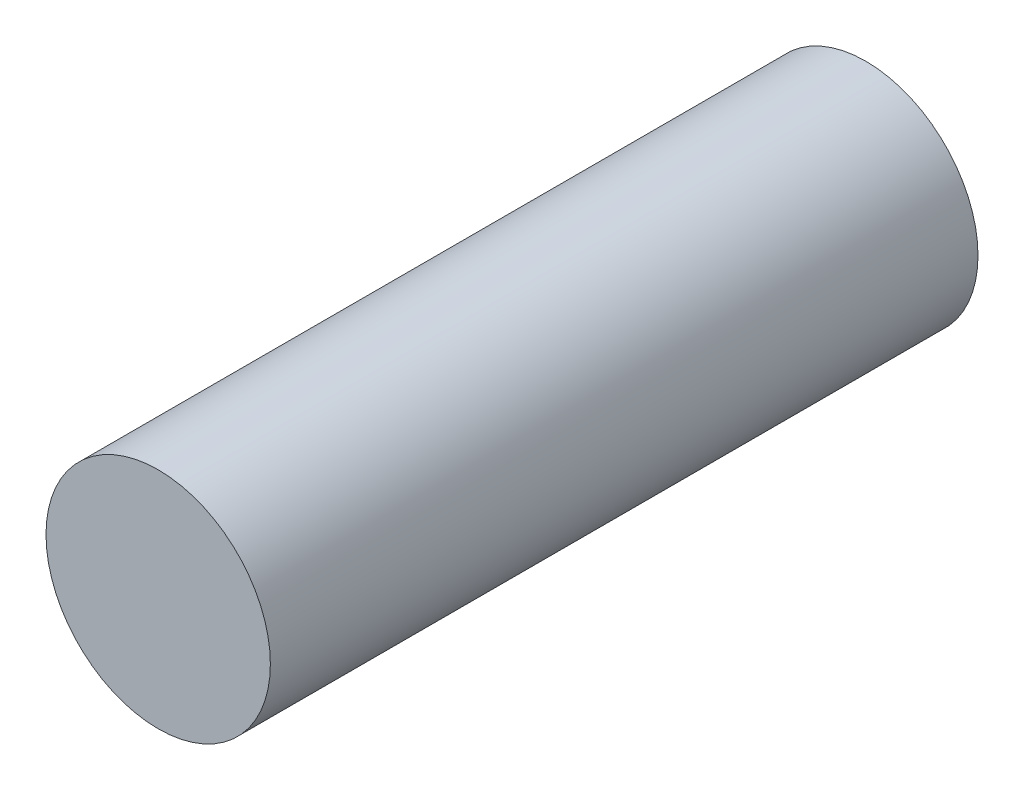
SolidWorks part; units mm, degrees
material "Polyester Resin"
ref_plane "Front Plane" through (0, 0, 0) normal (0, 0, 1) x (1, 0, 0)
ref_plane "Top Plane" through (0, 0, 0) normal (0, 1, 0) x (1, 0, 0)
ref_plane "Right Plane" through (0, 0, 0) normal (1, 0, 0) x (0, 0, -1)
ref_axis "x-axis" through (88.99, 0, 0) along (-1, 0, 0)
ref_axis "y-axis" through (0, 0, 55) along (0, 0, -1)
ref_axis "z-axis" through (0, 55, 0) along (0, -1, 0)
sketch "Sketch1" plane through (0, 0, 0) normal (0, 0, 1) x (1, 0, 0)
  circle A0 centre (0, 0) radius 6.5
  dimension "D1" = 13
extrude "battery" add sketch "Sketch1" against normal mid plane 41
